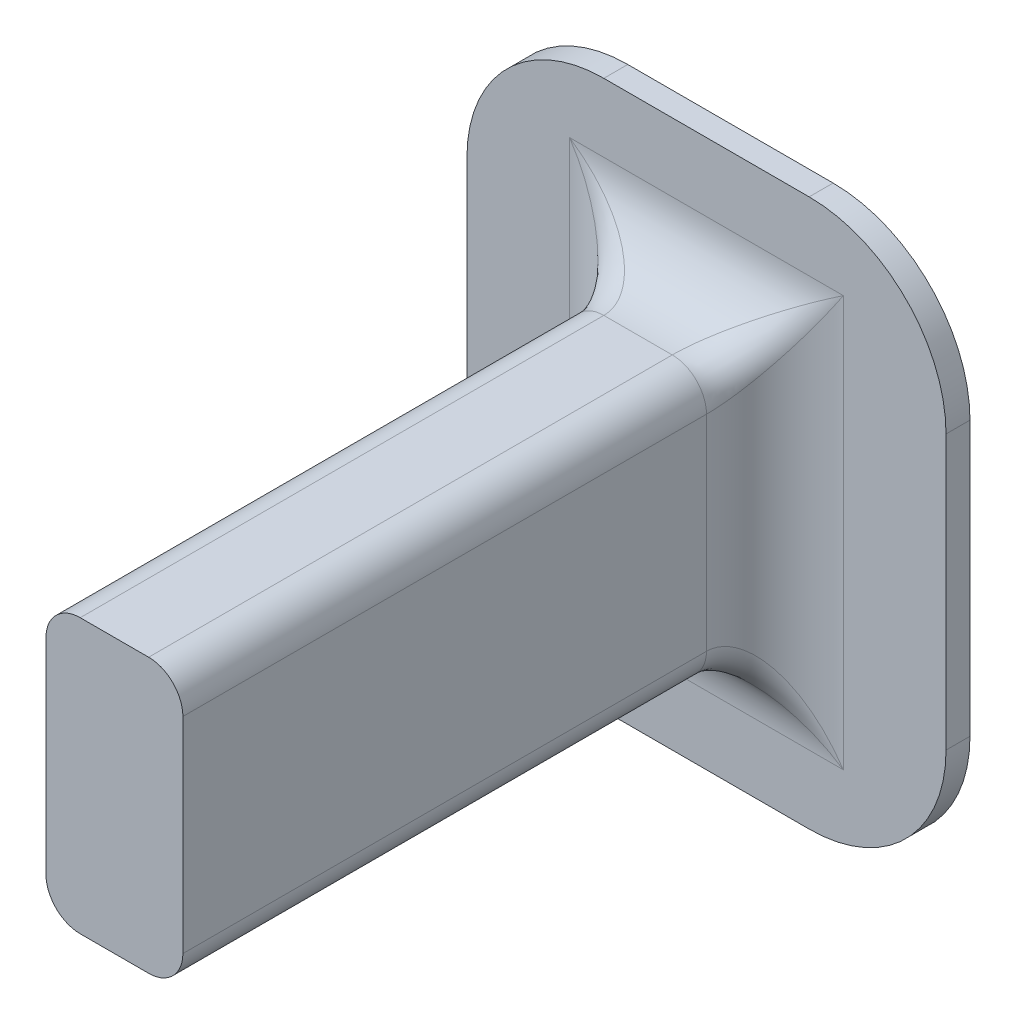
SolidWorks part; units mm, degrees
ref_plane "正面" through (0, 0, 0) normal (0, 0, 1) x (1, 0, 0)
ref_plane "平面" through (0, 0, 0) normal (0, 1, 0) x (1, 0, 0)
ref_plane "右側面" through (0, 0, 0) normal (1, 0, 0) x (0, 0, -1)
sketch "ｽｹｯﾁ1" plane through (0, 0, 0) normal (0, 0, 1) x (1, 0, 0)
  line L1 (0, 0) -> (70, 0)
  line L2 (0, 0) -> (0, 80)
  line L3 (0, 80) -> (70, 80)
  line L4 (70, 0) -> (70, 80)
  dimension "D1" = 70
  dimension "D2" = 80
extrude "ﾎﾞｽ - 押し出し1" add sketch "ｽｹｯﾁ1" along normal blind 3.5
sketch "ｽｹｯﾁ2" plane through (0, 0, 3.5) normal (0, 0, 1) x (1, 0, 0)
  line L0 (0, 40) -> (70, 40) construction
  line L1 (0, 80) -> (0, 0) construction
  line L2 (70, 0) -> (70, 80) construction
  line L3 (35, 80) -> (35, 0) construction
  line L4 (70, 80) -> (0, 80) construction
  line L5 (0, 0) -> (70, 0) construction
  line L7 (25, 20) -> (45, 20)
  line L8 (25, 20) -> (25, 60)
  line L9 (25, 60) -> (45, 60)
  line L10 (45, 20) -> (45, 60)
  line L11 (25, 20) -> (45, 60) construction
  line L12 (25, 60) -> (45, 20) construction
  point P12 (35, 40)
  dimension "D1" = 20
  dimension "D2" = 40
extrude "ﾎﾞｽ - 押し出し2" add sketch "ｽｹｯﾁ2" along normal blind 86.5
fillet "ﾌｨﾚｯﾄ1" radius 20 4 edges at (70, 0, 1.75) (0, 0, 1.75) (0, 80, 1.75) (70, 80, 1.75)
fillet "ﾌｨﾚｯﾄ2" radius 10 4 edges at (35, 20, 3.5) (25, 40, 3.5) (35, 60, 3.5) (45, 40, 3.5)
fillet "ﾌｨﾚｯﾄ3" radius 5 8 edges at (22.0711, 17.0711, 6.4289) (47.9289, 17.0711, 6.4289) (22.0711, 62.9289, 6.4289) (47.9289, 62.9289, 6.4289) (25, 20, 51.75) (45, 20, 51.75) (25, 60, 51.75) (45, 60, 51.75)
